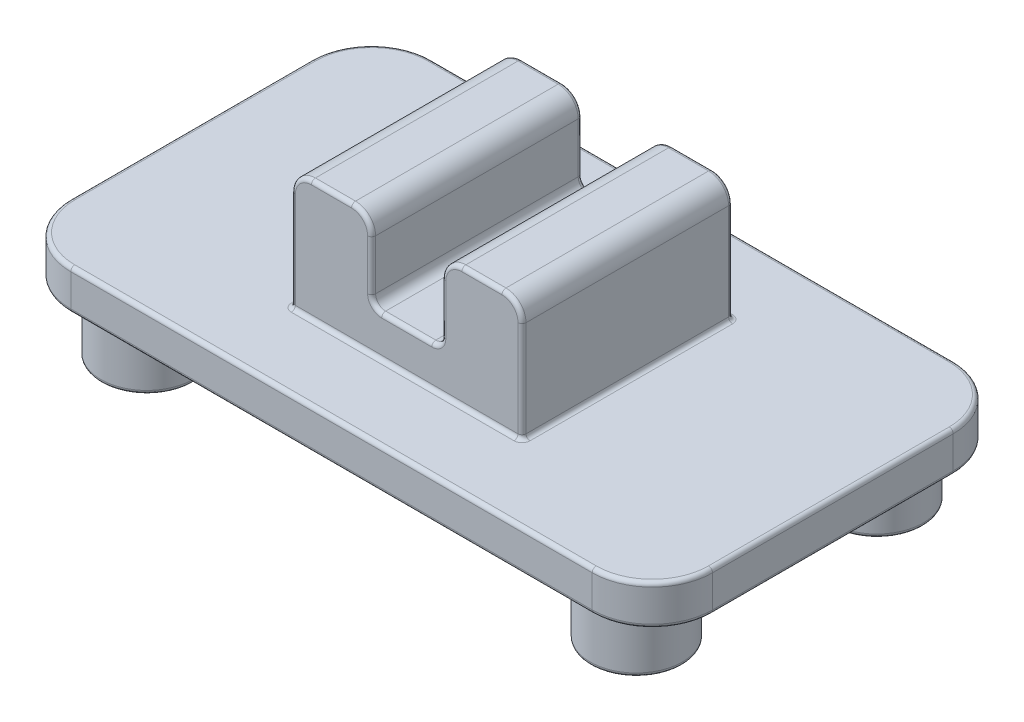
SolidWorks part; units mm, degrees
ref_plane "Front Plane" through (0, 0, 0) normal (0, 0, 1) x (1, 0, 0)
ref_plane "Top Plane" through (0, 0, 0) normal (0, 1, 0) x (1, 0, 0)
ref_plane "Right Plane" through (0, 0, 0) normal (1, 0, 0) x (0, 0, -1)
sketch "Sketch2" plane through (0, 0, 0) normal (0, 1, 0) x (1, 0, 0)
  line L1 (0, 0) -> (16, 0)
  line L2 (0, 0) -> (0, 9)
  line L3 (0, 9) -> (16, 9)
  line L4 (16, 0) -> (16, 9)
  dimension "D1" = 9
  dimension "D2" = 16
extrude "Boss-Extrude1" add sketch "Sketch2" along normal blind 1
sketch "Sketch3" plane through (0, 0, 0) normal (0, -1, 0) x (1, 0, 0)
  line L0 (16, -9) -> (0, -9) construction
  line L1 (0, -9) -> (0, 0) construction
  line L2 (16, 0) -> (16, -9) construction
  line L3 (0, 0) -> (16, 0) construction
  circle A0 centre (1.9, -1.5) radius 1.15
  circle A1 centre (14.1, -1.5) radius 1.15
  circle A2 centre (14.1, -7.5) radius 1.15
  circle A3 centre (1.9, -7.5) radius 1.15
  circle A4 centre (8, -4.5) radius 3
  circle A5 centre (8, -4.5) radius 1.5
  dimension "D1" = 2.3
  dimension "D2" = 2.3
  dimension "D3" = 2.3
  dimension "D4" = 2.3
  dimension "D13" = 6
  dimension "D14" = 3
  dimension "D5" = 1.5
  dimension "D6" = 1.9
  dimension "D7" = 1.5
  dimension "D8" = 1.9
  dimension "D9" = 1.5
  dimension "D10" = 1.9
  dimension "D11" = 1.5
  dimension "D12" = 1.9
  dimension "D15" = 4.5
  dimension "D16" = 8
extrude "Boss-Extrude2" add sketch "Sketch3" along normal blind 1.5
sketch "Sketch6" plane through (0, 1, 0) normal (0, 1, 0) x (1, 0, 0)
  line L0 (0, 0) -> (16, 0) construction
  line L1 (5.125, 1.875) -> (10.875, 1.875)
  line L2 (5.125, 1.875) -> (5.125, 7.125)
  line L3 (5.125, 7.125) -> (10.875, 7.125)
  line L4 (10.875, 1.875) -> (10.875, 7.125)
  line L5 (0, 9) -> (0, 0) construction
  dimension "D1" = 5.25
  dimension "D2" = 5.75
  dimension "D3" = 1.875
  dimension "D4" = 5.125
extrude "Boss-Extrude3" add sketch "Sketch6" along normal blind 1
sketch "Sketch7" plane through (0, 2, 0) normal (0, 1, 0) x (1, 0, 0)
  line L0 (5.125, 1.875) -> (10.875, 1.875) construction
  line L1 (5.125, 7.125) -> (7.125, 7.125)
  line L2 (5.125, 7.125) -> (5.125, 1.875)
  line L3 (5.125, 1.875) -> (7.125, 1.875)
  line L4 (7.125, 7.125) -> (7.125, 1.875)
  line L5 (10.875, 7.125) -> (5.125, 7.125) construction
  line L6 (10.875, 1.875) -> (8.875, 1.875)
  line L7 (10.875, 1.875) -> (10.875, 7.125)
  line L8 (10.875, 7.125) -> (8.875, 7.125)
  line L9 (8.875, 1.875) -> (8.875, 7.125)
  dimension "D1" = 2
  dimension "D2" = 2
extrude "Boss-Extrude4" add sketch "Sketch7" along normal blind 2
fillet "Fillet1" radius 0.5 4 edges at (10.875, 4, -4.5) (8.875, 4, -4.5) (7.125, 4, -4.5) (5.125, 4, -4.5)
fillet "Fillet2" radius 0.25 2 edges at (8.875, 2, -4.5)
fillet "Fillet3" radius 1.5 4 edges at (16, 0.5, -9) (16, 0.5, 0) (0, 0.5, -9) (0, 0.5, 0)
fillet "Fillet4" radius 0.1 56 edges at (8, 1, -7.125) (0.4393, 1, -0.4393) (0, 1, -4.5) (0.4393, 1, -8.5607) (8, 1, -9) (15.5607, 1, -8.5607) (16, 1, -4.5) (15.5607, 1, -0.4393) (5.2714, 3.8536, -7.125) (6.125, 4, -7.125) (6.9786, 3.8536, -7.125) (7.1982, 2.0732, -7.125) (8.8018, 2.0732, -7.125) (8.875, 2.875, -7.125) (9.0214, 3.8536, -7.125) (9.875, 4, -7.125) (10.7286, 3.8536, -7.125) (14.1, -1.5, -8.65) (8, 0, -7.5) (0.4393, 0, -8.5607) (0, 0, -4.5) (0.4393, 0, -0.4393) (15.5607, 0, -0.4393) (16, 0, -4.5) (15.5607, 0, -8.5607) (8, 0, -9) (14.1, 0, -8.65) (1.9, 0, -8.65) (1.9, -1.5, -8.65) (1.9, 0, -2.65) (1.9, -1.5, -2.65) (14.1, 0, -2.65) (14.1, -1.5, -2.65) (8, 1, 0) (8, 0, 0) (5.125, 1, -4.5) (5.125, 2.25, -7.125) (10.875, 1, -4.5) (10.875, 2.25, -7.125) (8, 1, -1.875) (5.125, 2.25, -1.875) (5.2714, 3.8536, -1.875) (6.125, 4, -1.875) (6.9786, 3.8536, -1.875) (7.1982, 2.0732, -1.875) (8.8018, 2.0732, -1.875) (8.875, 2.875, -1.875) (9.0214, 3.8536, -1.875) (9.875, 4, -1.875) (10.7286, 3.8536, -1.875) (10.875, 2.25, -1.875) (8, -1.5, -6)
fillet "Fillet5" radius 0.1 1 edges at (8, -1.5, -7.5)
fillet "Fillet6" radius 0.1 1 edges at (8, 0, -6)
